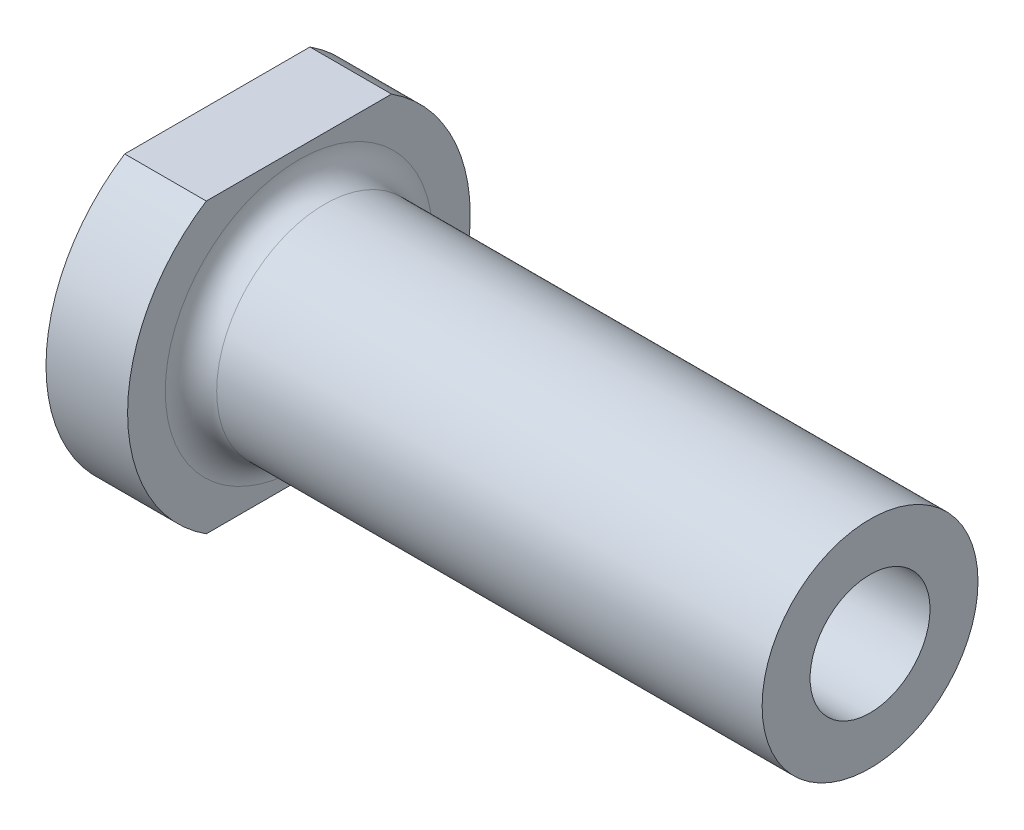
SolidWorks part; units mm, degrees
material "Ti-6Al-4VSolution treated and aged (SS)"
ref_plane "Front Plane" through (0, 0, 0) normal (0, 0, 1) x (1, 0, 0)
ref_plane "Top Plane" through (0, 0, 0) normal (0, 1, 0) x (1, 0, 0)
ref_plane "Right Plane" through (0, 0, 0) normal (1, 0, 0) x (0, 0, -1)
sketch "Sketch1" plane through (0, 0, 0) normal (0, 0, 1) x (1, 0, 0)
  line L0 (0, 0) -> (-17.6508, 0) construction
  line L1 (0, 0) -> (38.1, 0)
  line L2 (38.1, 0) -> (38.1, 6.3)
  line L3 (38.1, 6.3) -> (4.7625, 6.3)
  line L4 (4.7625, 6.3) -> (4.7625, 10)
  line L5 (4.7625, 10) -> (0, 10)
  line L6 (0, 10) -> (0, 0)
  dimension "D1" = 12.6
  dimension "D2" = 38.1
  dimension "D3" = 4.7625
  dimension "D4" = 20
revolve "Revolve1" add sketch "Sketch1" angle 360 about L0
fillet "Fillet1" radius 1.5 1 edges at (4.7625, 0, -6.3)
hole_wizard "5/16-18 MAKE SURE TO CHANGE THIS" positions "Sketch2" profile "Sketch3" tap size "M8x1.0" standard "ANSI Metric" end condition through all
sketch "Sketch2" plane through (38.1, 0, 0) normal (1, 0, 0) x (0, 0, -1)
  point P0 (0, 0)
sketch "Sketch3" plane through (38.1, 0, 0) normal (0, 1, 0) x (0, 0, -1)
  line L0 (0, 0) -> (0, 38.1)
  line L1 (0, 38.1) -> (3.5, 38.1)
  line L2 (3.5, 38.1) -> (3.5, 0)
  line L5 (3.5, 0) -> (0, 0)
  line L11 (0, -6.35) -> (0, 107.95) construction
  dimension "Thru Tap Drill Dia." = 7
  dimension "Thru Tap Drill Depth" = 38.1
cosmetic thread "Hole Thread1" parameters "D2"=8
sketch "Sketch4" plane through (0, 0, 0) normal (-1, 0, 0) x (0, 0, 1)
  line L0 (-5.4065, 8.4125) -> (5.4065, 8.4125)
  line L5 (5.4065, -8.4125) -> (-5.4065, -8.4125)
  arc A1 (5.4065, 8.4125) -> (-5.4065, 8.4125) centre (0, 0) ccw
  circle A2 centre (0, 0) radius 10
  arc A3 (-5.4065, -8.4125) -> (5.4065, -8.4125) centre (0, 0) ccw
  point P4 (0, 10)
  dimension "D1" = 0
  dimension "D2" = 1.5875
extrude "Cut-Extrude1" cut sketch "Sketch4" against normal through all
equation "\"D4@Sketch1\"=20mm"
equation "\"D1@Sketch1\"=0.500000in-0.1mm"
